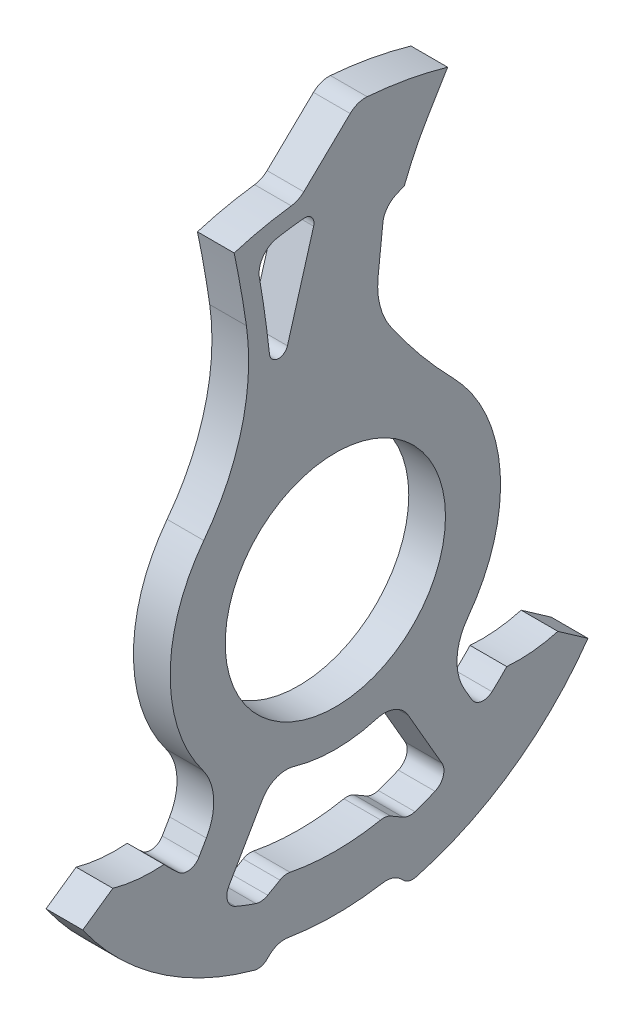
SolidWorks part; units mm, degrees
material "AR500"
ref_plane "Front Plane" through (0, 0, 0) normal (0, 0, 1) x (1, 0, 0)
ref_plane "Top Plane" through (0, 0, 0) normal (0, 1, 0) x (1, 0, 0)
ref_plane "Right Plane" through (0, 0, 0) normal (1, 0, 0) x (0, 0, -1)
other "Center of Mass"
sketch "Sketch1" plane through (0, 0, 0) normal (1, 0, 0) x (0, 0, -1)
  circle A0 centre (0, 0) radius 139.7 construction
  circle A1 centre (0, 0) radius 106.68 construction
  circle A2 centre (0, 0) radius 38.1 construction
  dimension "D1" = 279.4
  dimension "D2" = 33.02
  dimension "D3" = 76.2
sketch "Sketch2" plane through (0, 0, 0) normal (1, 0, 0) x (0, 0, -1)
  line L0 (0, 0) -> (38.858, 134.187) construction
  line L1 (38.858, 134.187) -> (32.2885, 123.3181)
  line L2 (0, 0) -> (0, 61.679) construction
  line L3 (7.5549, 139.4956) -> (-12.768, 119.9725)
  line L4 (-35.0051, 115.4602) -> (-40.3483, 140.8902) construction
  line L5 (23.88, 106.192) -> (20.1469, 96.5425) construction
  line L6 (23.88, 106.192) -> (16.9106, 103.1109)
  line L7 (16.9106, 103.1109) -> (14.7878, 83.4098)
  line L8 (-35.0051, 115.4602) -> (-4.6687, 124.6576) construction
  line L10 (0, -100.33) -> (0, 0) construction
  line L11 (-20.0866, -98.2987) -> (-25.4, -103.6121)
  line L16 (-49.9001, -64.1593) -> (-37.6706, -42.9773)
  line L17 (87.3871, -61.1891) -> (76.9839, -53.9047)
  line L18 (-87.3871, -61.1891) -> (-76.9839, -53.9047)
  line L19 (49.9001, -64.1593) -> (37.6706, -42.9773)
  line L24 (53.8815, -53.8815) -> (0, 0) construction
  line L25 (20.0866, -98.2987) -> (25.4, -103.6121)
  circle A0 centre (0, 0) radius 139.7 construction
  arc A1 (38.858, 134.187) -> (7.5549, 139.4956) centre (0, 0) ccw
  arc A2 (-12.768, 119.9725) -> (-35.0051, 115.4602) centre (0, 0) ccw
  arc A3 (32.2885, 123.3181) -> (23.88, 106.192) centre (125.9607, 66.6999) ccw
  arc A4 (40.8562, 39.9611) -> (37.6706, -42.9773) centre (0, 0) cw
  circle A5 centre (0, 0) radius 38.1 construction
  arc A6 (19.1729, 66.2092) -> (14.7878, 83.4098) centre (40.0416, 80.6887) cw
  arc A7 (-35.0051, 115.4602) -> (-30.7712, 91.5455) centre (-407.8633, 37.1165) cw
  arc A8 (-30.7712, 91.5455) -> (-45.5098, 34.5685) centre (-106.1896, 80.6597) cw
  arc A9 (-45.5098, 34.5685) -> (-37.6706, -42.9773) centre (0, 0) ccw
  arc A10 (-87.3871, -61.1891) -> (-25.4, -103.6121) centre (0, 0) ccw
  circle A11 centre (0, 0) radius 106.68 construction
  arc A18 (-76.9839, -53.9047) -> (-59.2852, -55.6031) centre (-63.357, -4.9665) ccw
  arc A19 (-59.2852, -55.6031) -> (-49.9001, -64.1593) centre (0, 0) ccw
  arc A20 (-20.0866, -98.2987) -> (20.0866, -98.2987) centre (0, 0) ccw
  arc A21 (59.2852, -55.6031) -> (49.9001, -64.1593) centre (0, 0) cw
  arc A22 (76.9839, -53.9047) -> (59.2852, -55.6031) centre (63.357, -4.9665) cw
  arc A23 (87.3871, -61.1891) -> (25.4, -103.6121) centre (0, 0) cw
  circle A24 centre (0, 0) radius 38.1
  arc A25 (19.1729, 66.2092) -> (40.8562, 39.9611) centre (186.1228, 182.0451) ccw
  dimension "D4" = 19.05
  dimension "D11" = 57.15
  dimension "D13" = 25.4
  dimension "D14" = 381
  dimension "D16" = 76.2
  dimension "D19" = 6.35
  dimension "D21" = 55
  dimension "D26" = 17.78
  dimension "D22" = 25.4
  dimension "D23" = 50.8
  dimension "D27" = 12.7
  dimension "D29" = 203.2
  dimension "D1" = 15
  dimension "D2" = 16.15
  dimension "D3" = 15
  dimension "D5" = 31.75
  dimension "D6" = 12.7
  dimension "D7" = 31.75
  dimension "D8" = 5
  dimension "D9" = 45
  dimension "D10" = 10
  dimension "D12" = 7.62
  dimension "D15" = 85
  dimension "D17" = 76.2
  dimension "D18" = 25.4
  dimension "D20" = 45
  dimension "D24" = 12.7
  dimension "D25" = 45
  dimension "D28" = 30
extrude "Boss-Extrude1" add sketch "Sketch2" along normal mid plane 12.7
sketch "Sketch3" plane through (6.35, 0, 0) normal (1, 0, 0) x (0, 0, -1)
  line L1 (-7.513, 109.7387) -> (-16.5762, 78.441)
  line L2 (14.7878, 83.4098) -> (16.9106, 103.1109) construction
  line L3 (-3.2803, 66.3447) -> (4.4504, 105.5668) construction
  line L4 (16.9106, 103.1109) -> (-8.0099, 108.0227) construction
  arc A0 (-12.768, 119.9725) -> (-35.0051, 115.4602) centre (0, 0) ccw construction
  arc A1 (-30.7712, 91.5455) -> (-35.0051, 115.4602) centre (-407.8633, 37.1165) ccw construction
  arc A2 (-7.513, 109.7387) -> (-10.8645, 113.7825) centre (-10.5627, 110.6219) ccw
  arc A3 (-12.768, 119.9725) -> (-35.0051, 115.4602) centre (0, 0) ccw construction
  arc A4 (-30.7712, 91.5455) -> (-35.0051, 115.4602) centre (-407.8633, 37.1165) ccw construction
  arc A5 (-10.8645, 113.7825) -> (-27.6085, 110.9156) centre (0, 0) ccw
  arc A6 (-22.7823, 78.981) -> (-27.6085, 110.9156) centre (-407.8633, 37.1165) ccw
  arc A7 (-24.4863, 92.4527) -> (-27.6085, 110.9156) centre (-407.8633, 37.1165) ccw construction
  arc A8 (-12.096, 113.6582) -> (-27.6085, 110.9156) centre (0, 0) ccw construction
  arc A14 (-22.7823, 78.981) -> (-16.5762, 78.441) centre (-19.6259, 79.3242) ccw
  point P18 (16.9106, 103.1109)
  dimension "D5" = 3.175
  dimension "D7" = 3.175
  dimension "D3" = 10
  dimension "D4" = 25.4
  dimension "D1" = 6.35
extrude "Cut-Extrude1" cut sketch "Sketch3" against normal through all
fillet "Fillet1" radius 7.62 6 edges at (0, 103.1109, -16.9106) (0, 110.9156, 27.6085) (0, 139.4956, -7.5549) (0, 119.9725, 12.768) (0, -98.2987, -20.0866) (0, -98.2987, 20.0866)
fillet "Fillet4" radius 19.05 2 edges at (0, -42.9773, -37.6706) (0, -42.9773, 37.6706)
fillet "Fillet2" radius 4.572 4 edges at (0, -103.6121, 25.4) (0, -103.6121, -25.4) (0, -64.1593, -49.9001) (0, -64.1593, 49.9001)
sketch "Sketch4" plane through (6.35, 0, 0) normal (1, 0, 0) x (0, 0, -1)
  line L0 (-21.1843, -46.1721) -> (-39.646, -78.1487)
  line L1 (-44.6265, -55.0252) -> (-47.1846, -59.4559) construction
  line L2 (0, -81.28) -> (0, -50.8)
  line L3 (-25.3274, -83.8901) -> (-17.5035, -79.373)
  line L4 (-11.6185, -94.3061) -> (-25.8749, -102.5371) construction
  arc A0 (-39.646, -78.1487) -> (-25.3274, -83.8901) centre (0, 0) ccw
  arc A1 (0, -50.8) -> (-21.1843, -46.1721) centre (0, 0) cw
  circle A2 centre (0, 0) radius 38.1 construction
  circle A3 centre (0, 0) radius 106.68 construction
  arc A4 (-17.5035, -79.373) -> (0, -81.28) centre (0, 0) ccw
  arc A5 (-16.2916, -98.9984) -> (16.2916, -98.9984) centre (0, 0) ccw construction
  arc A6 (-87.3871, -61.1891) -> (-27.9851, -102.9439) centre (0, 0) ccw construction
  arc A7 (-16.2916, -98.9984) -> (-22.9171, -101.1292) centre (-17.5289, -106.5173) ccw construction
  dimension "D1" = 50.8
  dimension "D3" = 19.05
  dimension "D4" = 19.05
  dimension "D2" = 15.875
  dimension "D5" = 30
  dimension "D6" = 15.875
extrude "Cut-Extrude2" cut sketch "Sketch4" against normal through all
mirror "Mirror1" about plane through (-6.35, -81.28, 0) normal (0, 0, -1) of "Cut-Extrude2"
fillet "Fillet3" radius 5.08 6 edges at (0, -78.1487, -39.646) (0, -83.8901, -25.3274) (0, -79.373, -17.5035) (0, -79.373, 17.5035) (0, -83.8901, 25.3274) (0, -78.1487, 39.646)
fillet "Fillet5" radius 9.525 2 edges at (0, -46.1721, -21.1843) (0, -46.1721, 21.1843)
ref_axis "Axis1" through (6.35, 0, 0) along (-1, 0, 0)
